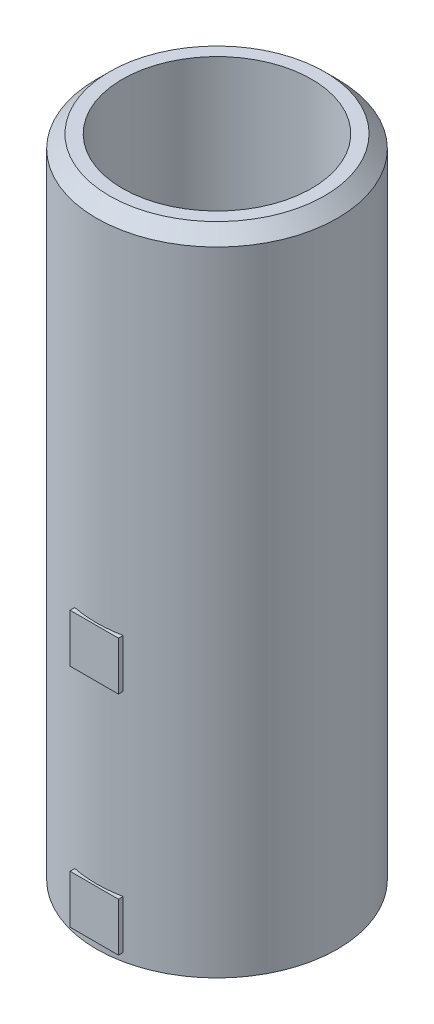
SolidWorks part; units mm, degrees
ref_plane "Front Plane" through (0, 0, 0) normal (0, 0, 1) x (1, 0, 0)
ref_plane "Top Plane" through (0, 0, 0) normal (0, 1, 0) x (1, 0, 0)
ref_plane "Right Plane" through (0, 0, 0) normal (1, 0, 0) x (0, 0, -1)
sketch "Sketch1" plane through (0, 0, 0) normal (0, 1, 0) x (1, 0, 0)
  circle A0 centre (0, 0) radius 14.5 construction
  circle A1 centre (0, 0) radius 14.65
  circle A2 centre (0, 0) radius 18.65
  dimension "D1" = 29
  dimension "D2" = 0.15
  dimension "D3" = 4.15
extrude "Boss-Extrude1" add sketch "Sketch1" along normal blind 100
ref_plane "Plane2" through (0, 0, 18.65) normal (0, 0, 1) x (1, 0, 0)
sketch "Sketch3" plane through (0, 0, 18.65) normal (0, 0, 1) x (1, 0, 0)
  line L0 (-18.65, 0) -> (18.65, 0) construction
  line L1 (18.65, 100) -> (-18.65, 100) construction
  line L2 (-18.65, 0) -> (18.65, 0) construction
  line L3 (18.65, 100) -> (-18.65, 100) construction
  line L4 (0, 100) -> (0, 0) construction
  line L5 (-3.75, 1.25) -> (3.75, 1.25)
  line L6 (-3.75, 1.25) -> (-3.75, 8.75)
  line L7 (-3.75, 8.75) -> (3.75, 8.75)
  line L8 (3.75, 1.25) -> (3.75, 8.75)
  line L9 (-3.75, 1.25) -> (3.75, 8.75) construction
  line L10 (-3.75, 8.75) -> (3.75, 1.25) construction
  line L11 (-3.75, 36.25) -> (3.75, 36.25)
  line L12 (-3.75, 36.25) -> (-3.75, 43.75)
  line L13 (-3.75, 43.75) -> (3.75, 43.75)
  line L14 (3.75, 36.25) -> (3.75, 43.75)
  line L15 (-3.75, 36.25) -> (3.75, 43.75) construction
  line L16 (-3.75, 43.75) -> (3.75, 36.25) construction
  point P4 (0, 5)
  point P9 (0, 40)
  point P17 (0, 41.0263)
  point P18 (0, 8.9978)
  point P19 (0, 8.8763)
  point P20 (5.0758, 36.25)
  point P21 (0, 40)
  point P22 (0, 100)
  point P23 (0, 5)
  point P24 (0, 40)
  point P25 (0, 40)
  dimension "D1" = 7.5
  dimension "D2" = 7.5
  dimension "D3" = 7.5
  dimension "D4" = 7.5
  dimension "D5" = 5
  dimension "D6" = 40
extrude "Boss-Extrude2" add sketch "Sketch3" against normal up to surface and the other way blind 0.35 up to face at (0, 100, 18.65)
ref_plane "Plane3" through (0, 0, -18.65) normal (0, 0, -1) x (-1, 0, 0)
sketch "Sketch4" plane through (0, 0, -18.65) normal (0, 0, -1) x (-1, 0, 0)
  line L4 (-3.75, 36.25) -> (3.75, 36.25)
  line L5 (-3.75, 43.75) -> (-3.75, 36.25)
  line L6 (3.75, 43.75) -> (-3.75, 43.75)
  line L7 (3.75, 36.25) -> (3.75, 43.75)
  line L8 (-3.75, 36.25) -> (3.75, 36.25)
  line L9 (-3.75, 43.75) -> (-3.75, 36.25)
  line L10 (3.75, 43.75) -> (-3.75, 43.75)
  line L11 (3.75, 36.25) -> (3.75, 43.75)
  dimension "D1" = 0
extrude "Boss-Extrude3" add sketch "Sketch4" against normal up to surface and the other way blind 0.35 up to face at (0, 40, 18.4595)
chamfer "Chamfer1" distance 2 angle 45 1 edges at (0, 100, 18.65)
equation "\"standoff_extrude\"=0.35"
equation "\"D2@Boss-Extrude2\"=\"standoff_extrude\""
equation "\"D2@Boss-Extrude3\"=\"standoff_extrude\""
